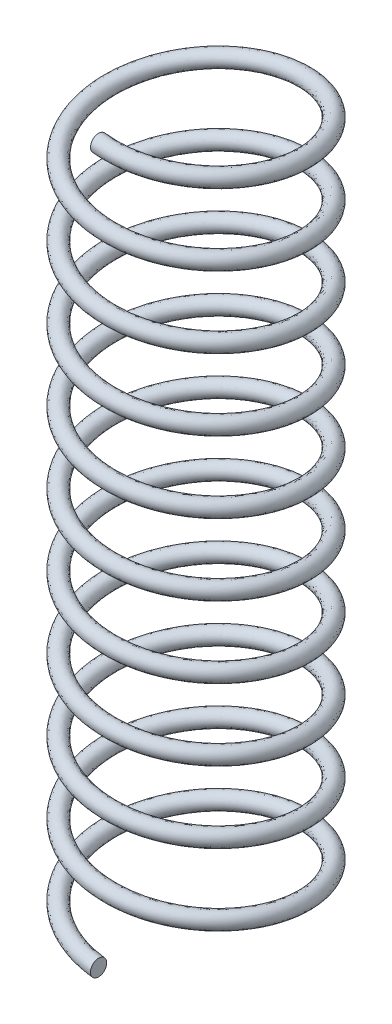
SolidWorks part; units mm, degrees
ref_plane "Front" through (0, 0, 0) normal (0, 0, 1) x (1, 0, 0)
ref_plane "Top" through (0, 0, 0) normal (0, 1, 0) x (1, 0, 0)
ref_plane "Right" through (0, 0, 0) normal (1, 0, 0) x (0, 0, -1)
sketch "Sketch1" plane through (0, 0, 0) normal (0, 1, 0) x (1, 0, 0)
  circle A0 centre (0, 0) radius 4.5
  dimension "D1" = 9
curve "Helix/Spiral1" pitch 3.3 height 33 turns 10
sketch "Sketch2" plane through (0, 0, 0) normal (1, 0, 0) x (0, 0, -1)
  circle A0 centre (-4.5, 0) radius 0.375
  spline S0 degree 3 poles (-4.5, 0) (-4.5, 0.0683) (-4.2657, 0.2065) (-3.2648, 0.4124) (-1.7669, 0.6188) (0, 0.825) (1.7669, 1.0313) (3.2648, 1.2375) (4.2657, 1.4438) (4.6172, 1.65) (4.2657, 1.8563) (3.2648, 2.0625) (1.2676, 2.3375) (-1.2676, 2.6125) (-3.2648, 2.8875) (-4.2657, 3.0938) (-4.6172, 3.3) (-4.2657, 3.5063) (-3.2648, 3.7125) (-1.2676, 3.9875) (1.2676, 4.2625) (3.2648, 4.5375) (4.2657, 4.7437) (4.6172, 4.95) (4.2657, 5.1562) (3.2648, 5.3625) (1.2676, 5.6375) (-1.2676, 5.9125) (-3.2648, 6.1875) (-4.2657, 6.3937) (-4.6172, 6.6) (-4.2657, 6.8062) (-3.2648, 7.0125) (-1.2676, 7.2875) (1.2676, 7.5625) (3.2648, 7.8375) (4.2657, 8.0437) (4.6172, 8.25) (4.2657, 8.4562) (3.2648, 8.6625) (1.2676, 8.9375) (-1.2676, 9.2125) (-3.2648, 9.4875) (-4.2657, 9.6937) (-4.6172, 9.9) (-4.2657, 10.1062) (-3.2648, 10.3125) (-1.2676, 10.5875) (1.2676, 10.8625) (3.2648, 11.1375) (4.2657, 11.3437) (4.6172, 11.55) (4.2657, 11.7562) (3.2648, 11.9625) (1.2676, 12.2375) (-1.2676, 12.5125) (-3.2648, 12.7875) (-4.2657, 12.9937) (-4.6172, 13.2) (-4.2657, 13.4062) (-3.2648, 13.6125) (-1.2676, 13.8875) (1.2676, 14.1625) (3.2648, 14.4375) (4.2657, 14.6437) (4.6172, 14.85) (4.2657, 15.0562) (3.2648, 15.2625) (1.2676, 15.5375) (-1.2676, 15.8125) (-3.2648, 16.0875) (-4.2657, 16.2937) (-4.6172, 16.5) (-4.2657, 16.7062) (-3.2648, 16.9125) (-1.2676, 17.1875) (1.2676, 17.4625) (3.2648, 17.7375) (4.2657, 17.9438) (4.6172, 18.15) (4.2657, 18.3563) (3.2648, 18.5625) (1.2676, 18.8375) (-1.2676, 19.1125) (-3.2648, 19.3875) (-4.2657, 19.5938) (-4.6172, 19.8) (-4.2657, 20.0063) (-3.2648, 20.2125) (-1.2676, 20.4875) (1.2676, 20.7625) (3.2648, 21.0375) (4.2657, 21.2438) (4.6172, 21.45) (4.2657, 21.6563) (3.2648, 21.8625) (1.2676, 22.1375) (-1.2676, 22.4125) (-3.2648, 22.6875) (-4.2657, 22.8938) (-4.6172, 23.1) (-4.2657, 23.3063) (-3.2648, 23.5125) (-1.2676, 23.7875) (1.2676, 24.0625) (3.2648, 24.3375) (4.2657, 24.5438) (4.6172, 24.75) (4.2657, 24.9563) (3.2648, 25.1625) (1.2676, 25.4375) (-1.2676, 25.7125) (-3.2648, 25.9875) (-4.2657, 26.1938) (-4.6172, 26.4) (-4.2657, 26.6063) (-3.2648, 26.8125) (-1.2676, 27.0875) (1.2676, 27.3625) (3.2648, 27.6375) (4.2657, 27.8438) (4.6172, 28.05) (4.2657, 28.2563) (3.2648, 28.4625) (1.2676, 28.7375) (-1.2676, 29.0125) (-3.2648, 29.2875) (-4.2657, 29.4937) (-4.6172, 29.7) (-4.2657, 29.9062) (-3.2648, 30.1125) (-1.2676, 30.3875) (1.2676, 30.6625) (3.2648, 30.9375) (4.2657, 31.1437) (4.6172, 31.35) (4.2657, 31.5562) (3.2648, 31.7625) (1.7669, 31.9687) (0, 32.175) (-1.7669, 32.3812) (-3.2648, 32.5876) (-4.2657, 32.7935) (-4.5, 32.9317) (-4.5, 33) knots 0 0 0 0 0.00625 0.0125 0.01875 0.025 0.03125 0.0375 0.04375 0.05 0.05625 0.0625 0.06875 0.08125 0.0875 0.09375 0.1 0.10625 0.1125 0.11875 0.13125 0.1375 0.14375 0.15 0.15625 0.1625 0.16875 0.18125 0.1875 0.19375 0.2 0.20625 0.2125 0.21875 0.23125 0.2375 0.24375 0.25 0.25625 0.2625 0.26875 0.28125 0.2875 0.29375 0.3 0.30625 0.3125 0.31875 0.33125 0.3375 0.34375 0.35 0.35625 0.3625 0.36875 0.38125 0.3875 0.39375 0.4 0.40625 0.4125 0.41875 0.43125 0.4375 0.44375 0.45 0.45625 0.4625 0.46875 0.48125 0.4875 0.49375 0.5 0.50625 0.5125 0.51875 0.53125 0.5375 0.54375 0.55 0.55625 0.5625 0.56875 0.58125 0.5875 0.59375 0.6 0.60625 0.6125 0.61875 0.63125 0.6375 0.64375 0.65 0.65625 0.6625 0.66875 0.68125 0.6875 0.69375 0.7 0.70625 0.7125 0.71875 0.73125 0.7375 0.74375 0.75 0.75625 0.7625 0.76875 0.78125 0.7875 0.79375 0.8 0.80625 0.8125 0.81875 0.83125 0.8375 0.84375 0.85 0.85625 0.8625 0.86875 0.88125 0.8875 0.89375 0.9 0.90625 0.9125 0.91875 0.93125 0.9375 0.94375 0.95 0.95625 0.9625 0.96875 0.975 0.98125 0.9875 0.99375 1 1 1 1 construction
  point P4 (-4.5, 0)
  dimension "D1" = 0.75
  dimension "D2" = 4.5
sweep "Sweep1" add profiles "Sketch2" path "Helix/Spiral1"
